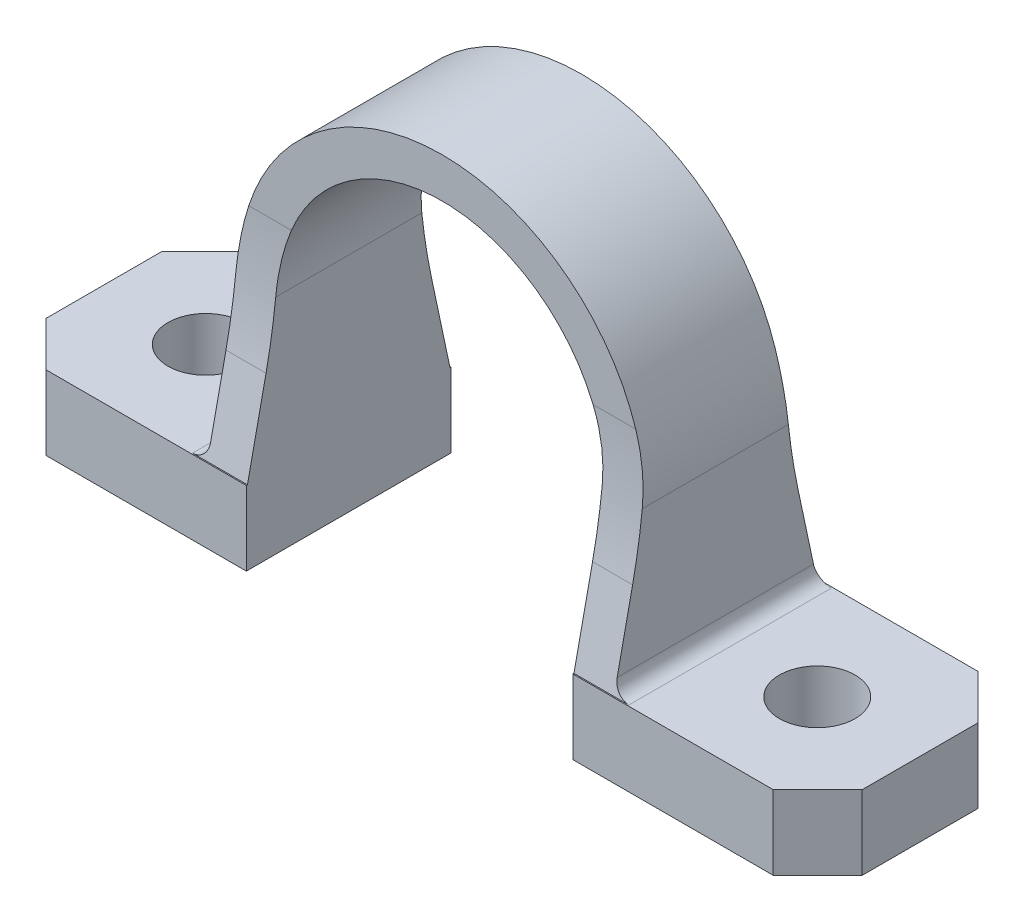
SolidWorks part; units mm, degrees
ref_plane "Front Plane" through (0, 0, 0) normal (0, 0, 1) x (1, 0, 0)
ref_plane "Top Plane" through (0, 0, 0) normal (0, 1, 0) x (1, 0, 0)
ref_plane "Right Plane" through (0, 0, 0) normal (1, 0, 0) x (0, 0, -1)
sketch "Sketch1" plane through (0, 0, 0) normal (0, 0, 1) x (1, 0, 0)
  line L0 (0, 18.3553) -> (0, -30.1974) construction
  line L1 (-13.7, 0) -> (-13.7, -10)
  line L2 (-27.5, -15) -> (27.5, -15)
  line L3 (-27.5, -15) -> (-27.5, -10)
  line L4 (-27.5, -10) -> (-13.7, -10)
  line L5 (27.5, -15) -> (27.5, -10)
  line L6 (-27.5, -15) -> (-11, -13.5) construction
  line L7 (-27.5, -10) -> (-11, -11.5) construction
  line L8 (13.7, 0) -> (13.7, -10)
  line L9 (11, 0) -> (11, -15)
  line L10 (-11, 0) -> (-11, -15)
  line L11 (-4.5826, -10) -> (4.5826, -10)
  line L12 (11, -11.5) -> (27.5, -10) construction
  line L13 (11, -13.5) -> (27.5, -15) construction
  line L14 (13.7, -10) -> (27.5, -10)
  circle A0 centre (0, 0) radius 11
  arc A1 (-4.5697, -12.9154) -> (0, -13.7) centre (0, 0) ccw
  arc A2 (13.7, 0) -> (-13.7, 0) centre (0, 0) ccw
  point P6 (0, -12.5)
  dimension "D3" = 2.7
  dimension "D4" = 22
  dimension "D1" = 5
  dimension "D2" = 15
  dimension "D5" = 55
extrude "Boss-Extrude1" add sketch "Sketch1" along normal blind 9.4 contours L8 A2 L1 L4 L3 L2 L10 A0 L9 L5 L14
sketch "Sketch2" plane through (0, 0, 9.4) normal (0, 0, 1) x (1, 0, 0)
  line L0 (11, 0) -> (11, -15) construction
  line L1 (-27.5, -10) -> (-11, -10)
  line L2 (-27.5, -10) -> (-27.5, -15)
  line L3 (-27.5, -15) -> (-11, -15)
  line L4 (-11, -10) -> (-11, -15)
  line L5 (27.5, -10) -> (11, -10)
  line L6 (27.5, -10) -> (27.5, -15)
  line L7 (27.5, -15) -> (11, -15)
  line L8 (11, -10) -> (11, -15)
extrude "Boss-Extrude2" add sketch "Sketch2" along normal blind 2.2
sketch "Sketch3" plane through (0, 0, 0) normal (0, 0, -1) x (-1, 0, 0)
  line L0 (-11, 0) -> (-11, -15) construction
  line L1 (-27.5, -10) -> (-11, -10)
  line L2 (-27.5, -10) -> (-27.5, -15)
  line L3 (-27.5, -15) -> (-11, -15)
  line L4 (-11, -10) -> (-11, -15)
  line L5 (-11, -15) -> (-27.5, -15) construction
  line L7 (11, -15) -> (27.5, -15)
  line L8 (11, -15) -> (11, -10)
  line L9 (11, -10) -> (27.5, -10)
  line L10 (27.5, -15) -> (27.5, -10)
extrude "Boss-Extrude3" add sketch "Sketch3" along normal blind 2.2
chamfer "Chamfer1" distance 10 angle 12 4 edges at (12.35, -10, 9.4) (-12.35, -10, 0)
chamfer "Chamfer2" distance 3 angle 45 4 edges at (-27.5, -12.5, -2.2) (-27.5, -12.5, 11.6) (27.5, -12.5, -2.2) (27.5, -12.5, 11.6)
fillet "Fillet1" radius 40 4 edges at (-12.35, 0, 0) (12.35, 0, 0) (-12.35, 0, 9.4) (12.35, 0, 9.4)
sketch "Sketch4" plane through (0, -10, 0) normal (0, 1, 0) x (1, 0, 0)
  line L0 (-26, -10.1) -> (-13.7, 2.1256) construction
  line L1 (-27.5, -8.6) -> (-24.5, -11.6) construction
  line L2 (-26, 0.7) -> (-13.7744, -11.6) construction
  line L3 (-24.5, 2.2) -> (-27.5, -0.8) construction
  line L4 (-11, -11.6) -> (-24.5, -11.6) construction
  line L5 (13.7, 2.1256) -> (26, -10.1) construction
  line L6 (24.5, -11.6) -> (27.5, -8.6) construction
  line L7 (13.7, -11.5256) -> (26, 0.7) construction
  line L8 (27.5, -0.8) -> (24.5, 2.2) construction
  circle A0 centre (-20.6001, -4.7328) radius 2.55
  circle A1 centre (20.5671, -4.7) radius 2.55
  dimension "D1" = 5.1
  dimension "D2" = 5.1
extrude "Cut-Extrude1" cut sketch "Sketch4" against normal through all
fillet "Fillet2" radius 1 2 edges
